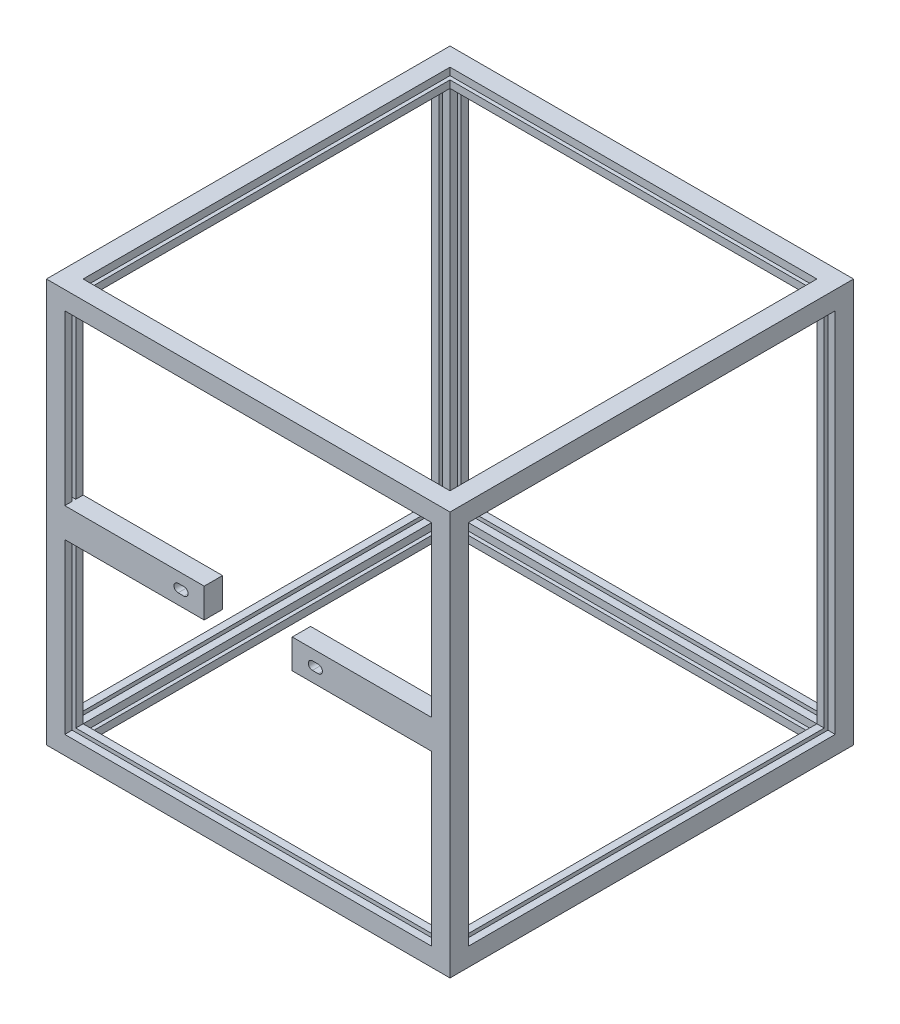
SolidWorks part; units mm, degrees
note: '?' marks a value the reader was unsure of.
ref_plane "Alzado" through (0, 0, 0) normal (0, 0, 1) x (1, 0, 0)
ref_plane "Planta" through (0, 0, 0) normal (0, 1, 0) x (1, 0, 0)
ref_plane "Vista lateral" through (0, 0, 0) normal (1, 0, 0) x (0, 0, -1)
sketch "Croquis1" plane through (0, 0, 0) normal (0, 0, 1) x (1, 0, 0)
  line L0 (5, -10) -> (5, 0) construction
  line L1 (0, 0) -> (10, 0)
  line L2 (0, 0) -> (0, -10)
  line L3 (0, -10) -> (10, -10)
  line L4 (10, 0) -> (10, -10)
  line L6 (10, -5) -> (0, -5) construction
  line L7 (4, -10) -> (6, -10)
  line L8 (4, -10) -> (4, -8)
  line L9 (4, -8) -> (6, -8)
  line L10 (6, -10) -> (6, -8)
  line L11 (10, 0) -> (210, 0)
  line L12 (10, 0) -> (10, -10)
  line L13 (10, -10) -> (210, -10)
  line L14 (210, 0) -> (210, -10)
  dimension "D1" = 10
  dimension "D2" = 10
  dimension "D3" = 2
  dimension "D4" = 1
  dimension "D5" = 2
  dimension "D6" = 200
sketch "Croquis2" plane through (0, 0, 0) normal (0, 0, 1) x (1, 0, 0)
  line L0 (10, -10) -> (10, -210)
  line L1 (0, 0) -> (220, 0)
  line L2 (0, 0) -> (0, -220)
  line L3 (0, -220) -> (220, -220)
  line L4 (220, 0) -> (220, -220)
  line L5 (10, -210) -> (210, -210)
  line L6 (210, -10) -> (210, -210)
  line L7 (10, -10) -> (210, -10)
  dimension "D1" = 220
  dimension "D2" = 220
  dimension "D3" = 10
extrude "Saliente-Extruir1" add sketch "Croquis2" along normal blind 10
sketch "Croquis3" plane through (0, 0, 10) normal (0, 0, 1) x (1, 0, 0)
  line L0 (0, -220) -> (10, -210) construction
  line L1 (10, -210) -> (210, -210) construction
  line L2 (220, 0) -> (210, -10) construction
  line L3 (216, -4) -> (216, -216)
  line L4 (215, -5) -> (5, -5)
  line L5 (215, -5) -> (215, -215)
  line L6 (215, -215) -> (5, -215)
  line L7 (5, -5) -> (5, -215)
  line L8 (216, -216) -> (4, -216)
  line L9 (4, -4) -> (4, -216)
  line L10 (216, -4) -> (4, -4)
  line L11 (214, -6) -> (214, -214)
  line L12 (214, -214) -> (6, -214)
  line L13 (6, -6) -> (6, -214)
  line L14 (214, -6) -> (6, -6)
  dimension "D1" = 1
  dimension "D2" = 1
extrude "Cortar-Extruir1" cut sketch "Croquis3" against normal blind 3.5 contours L3 L10 L9 L8 L7 L4 L5 L6 | L4 L7 L6 L5 L14 L11 L12 L13
sketch "Croquis4" plane through (0, 0, 10) normal (0, 0, 1) x (1, 0, 0)
  line L1 (0, 0) -> (10, 0)
  line L2 (0, 0) -> (0, -10)
  line L3 (0, -10) -> (10, -10)
  line L4 (10, 0) -> (10, -10)
  line L5 (220, 0) -> (210, 0)
  line L6 (220, 0) -> (220, -10)
  line L7 (220, -10) -> (210, -10)
  line L8 (210, 0) -> (210, -10)
  line L9 (210, -210) -> (220, -210)
  line L10 (210, -210) -> (210, -220)
  line L11 (210, -220) -> (220, -220)
  line L12 (220, -210) -> (220, -220)
  line L13 (10, -210) -> (0, -210)
  line L14 (10, -210) -> (10, -220)
  line L15 (10, -220) -> (0, -220)
  line L16 (0, -210) -> (0, -220)
extrude "Saliente-Extruir2" add sketch "Croquis4" along normal blind 200 and the other way blind 10
sketch "Croquis6" plane through (0, 0, 210) normal (0, 0, 1) x (1, 0, 0)
  line L1 (4, -10) -> (6, -10)
  line L2 (4, -10) -> (4, -6.5)
  line L3 (4, -6.5) -> (6, -6.5)
  line L4 (6, -10) -> (6, -6.5)
  line L5 (10, -4) -> (6.5, -4)
  line L6 (10, -4) -> (10, -6)
  line L7 (10, -6) -> (6.5, -6)
  line L8 (6.5, -4) -> (6.5, -6)
  line L9 (0, -220) -> (10, -220)
  line L10 (0, -220) -> (0, -210)
  line L11 (0, -210) -> (10, -210)
  line L12 (10, -220) -> (10, -210)
  line L13 (4, -210) -> (6, -210)
  line L14 (4, -210) -> (4, -213.5)
  line L15 (4, -213.5) -> (6, -213.5)
  line L16 (6, -210) -> (6, -213.5)
  line L17 (10, -214) -> (6.5, -214)
  line L18 (10, -214) -> (10, -216)
  line L19 (10, -216) -> (6.5, -216)
  line L20 (6.5, -214) -> (6.5, -216)
  line L21 (220, 0) -> (210, 0)
  line L22 (220, 0) -> (220, -10)
  line L23 (220, -10) -> (210, -10)
  line L24 (210, 0) -> (210, -10)
  line L25 (210, -4) -> (213.5, -4)
  line L26 (210, -4) -> (210, -6)
  line L27 (210, -6) -> (213.5, -6)
  line L28 (213.5, -4) -> (213.5, -6)
  line L29 (214, -10) -> (216, -10)
  line L30 (214, -10) -> (214, -6.5)
  line L31 (214, -6.5) -> (216, -6.5)
  line L32 (216, -10) -> (216, -6.5)
  line L33 (210, -210) -> (220, -210)
  line L34 (210, -210) -> (210, -220)
  line L35 (210, -220) -> (220, -220)
  line L36 (220, -210) -> (220, -220)
  line L37 (216, -210) -> (214.0019, -210)
  line L38 (216, -210) -> (216, -213.5)
  line L39 (216, -213.5) -> (214.0019, -213.5)
  line L40 (214.0019, -210) -> (214.0019, -213.5)
  line L41 (210, -214) -> (213.5, -214)
  line L42 (210, -214) -> (210, -216)
  line L43 (210, -216) -> (213.5, -216)
  line L44 (213.5, -214) -> (213.5, -216)
  line M3 (0, -10) -> (10, -10)
  line M4 (10, -10) -> (10, 0)
  dimension "D1" = 3.5
  dimension "D2" = 3.5
  dimension "D3" = 3.5
  dimension "D4" = 3.5
  dimension "D5" = 3.5
  dimension "D6" = 3.5
  dimension "D7" = 3.5
  dimension "D8" = 3.5
extrude "Cortar-Extruir2" cut sketch "Croquis6" against normal blind 203.5 contours L5 L8 L7 M4 | L4 L3 L2 M3 | L28 L25 L24 L27 | L23 L32 L31 L30 | L44 L41 L34 L43 | L33 L40 L39 L38 | L16 L11 L14 L15 | L17 L20 L19 L12
sketch "Croquis7" plane through (0, 0, 210) normal (0, 0, 1) x (1, 0, 0)
  line L1 (0, 0) -> (220, 0)
  line L2 (0, 0) -> (0, -220)
  line L3 (0, -220) -> (220, -220)
  line L4 (220, 0) -> (220, -220)
  line L5 (10, -10) -> (210, -10)
  line L6 (10, -10) -> (10, -210)
  line L7 (10, -210) -> (210, -210)
  line L8 (210, -10) -> (210, -210)
extrude "Saliente-Extruir3" add sketch "Croquis7" along normal blind 10
sketch "Croquis8" plane through (0, -210, 0) normal (0, 1, 0) x (1, 0, 0)
  line L0 (210, -210) -> (220, -220) construction
  line L1 (0, -220) -> (10, -210) construction
  line L2 (6.5, -215) -> (213.5, -215) construction
  line L3 (6.5, -216) -> (213.5, -216)
  line L4 (6.5, -214) -> (213.5, -214)
  line L5 (6.5, -214) -> (6.5, -216)
  line L6 (10, -220) -> (10, -210) construction
  line L7 (5, -214) -> (215, -214) construction
  line L8 (5, -215) -> (215, -215) construction
  line L9 (5, -216) -> (215, -216) construction
  line L10 (213.5, -214) -> (213.5, -216)
  line L11 (210, -220) -> (210, -210) construction
  dimension "D3" = 3.5
  dimension "D4" = 3.5
  dimension "D1" = 1
  dimension "D2" = 1
extrude "Cortar-Extruir3" cut sketch "Croquis8" against normal blind 3.5 and the other way blind 203.5 contours L4 L10 L3 L5
ref_plane "PlanoX" through (0, 0, 110) normal (0, 0, 1) x (1, 0, 0)
ref_plane "PlanoY" through (0, -110, 0) normal (0, 1, 0) x (1, 0, 0)
ref_plane "PlanoZ" through (110, 0, 0) normal (1, 0, 0) x (0, 0, -1)
ref_axis "EjeXY" through (-11, -110, 110) along (1, 0, 0)?
ref_axis "EjeYZ" through (110, -110, -11) along (0, 0, 1)?
ref_axis "EjeXZ" through (110, 11, 110) along (0, -1, 0)
pattern_circular "MatrizC1" count 4 over 360 about axis through (0, -110, 110) along (1, 0, 0) of "Cortar-Extruir3"
sketch "Croquis9" plane through (0, 0, 220) normal (0, 0, 1) x (1, 0, 0)
  line L0 (0, -110) -> (220, -110) construction
  line L1 (0, 0) -> (0, -220) construction
  line L2 (220, -220) -> (220, 0) construction
  line L3 (0, -118) -> (220, -118)
  line L4 (0, -102) -> (220, -102)
  line L5 (0, -102) -> (0, -118)
  line L6 (220, -118) -> (220, -102)
  line L7 (71.8015, -110) -> (75, -110) construction
  line L8 (71.8015, -107.75) -> (75, -107.75)
  line L9 (71.8015, -112.25) -> (75, -112.25)
  line L10 (86, -102) -> (86, -118)
  line L11 (110, -121) -> (110, 121) construction
  line L12 (134, -102) -> (134, -118)
  line L13 (148.1985, -110) -> (145, -110) construction
  line L14 (148.1985, -107.75) -> (145, -107.75)
  line L15 (148.1985, -112.25) -> (145, -112.25)
  arc A0 (71.8015, -107.75) -> (71.8015, -112.25) centre (71.8015, -110) ccw
  arc A1 (75, -112.25) -> (75, -107.75) centre (75, -110) ccw
  arc A2 (148.1985, -107.75) -> (148.1985, -112.25) centre (148.1985, -110) cw
  arc A3 (145, -112.25) -> (145, -107.75) centre (145, -110) cw
  point P12 (73.4008, -110)
  point P17 (110, -110)
  point P26 (146.5992, -110)
  dimension "D1" = 35
  dimension "D2" = 4.5
  dimension "D3" = 86
extrude "Brazos" add sketch "Croquis9" against normal blind 10 contours L10 L4 L7 L3 A1 L9 A0 L8 | L4 A1 L3 L7 | L4 L12 L3 L15 A3 L14 A2 | L4 L12 L3 L10
pattern_circular "MatrizC2" count 4 over 360 about axis through (110, 11, 110) along (0, -1, 0) of "Cortar-Extruir3"
